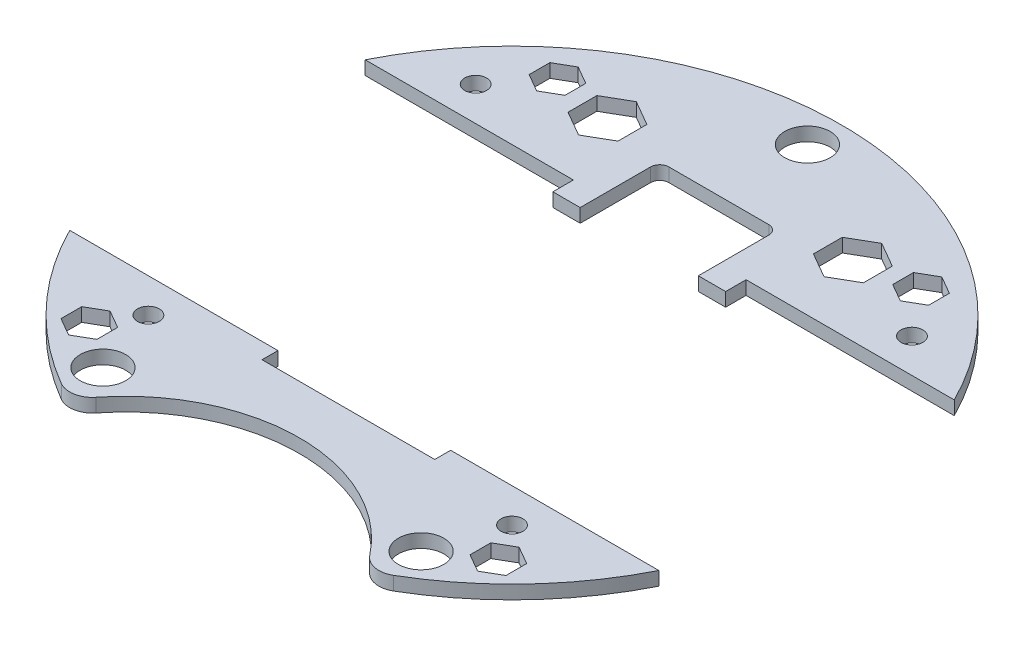
SolidWorks part; units mm, degrees
material "Acrylic (Medium-high impact)"
ref_plane "Front Plane" through (0, 0, 0) normal (0, 0, 1) x (1, 0, 0)
ref_plane "Top Plane" through (0, 0, 0) normal (0, 1, 0) x (1, 0, 0)
ref_plane "Right Plane" through (0, 0, 0) normal (1, 0, 0) x (0, 0, -1)
sketch "Sketch1" plane through (0, 0, 0) normal (0, 1, 0) x (1, 0, 0)
  line L0 (0, -85) -> (-32.4891, -64.8129) construction
  line L1 (0, -85) -> (0, 0) construction
  arc A0 (36.5434, -62.6165) -> (-36.5434, -62.6165) centre (0, 0) ccw
  arc A1 (30.0898, -61.3851) -> (-30.0898, -61.3851) centre (0, -85) ccw
  arc A2 (36.5434, -62.6165) -> (30.0898, -61.3851) centre (34.0231, -58.2982) cw
  arc A3 (-30.0898, -61.3851) -> (-36.5434, -62.6165) centre (-34.0231, -58.2982) cw
  dimension "D1" = 145
  dimension "D2" = 76.5
  dimension "D4" = 5
  dimension "D3" = 85
extrude "Boss-Extrude1" add sketch "Sketch1" along normal blind 3
sketch "solenoid placement" plane through (0, 3, 0) normal (0, 1, 0) x (1, 0, 0)
  line L4 (-19, -36) -> (19, -36)
  line L5 (-19, 28) -> (-19, -36)
  line L6 (19, 28) -> (-19, 28)
  line L7 (19, -36) -> (19, 28)
  line L8 (-19, -36) -> (19, -36)
  line L9 (-19, 28) -> (-19, -36)
  line L10 (19, 28) -> (-19, 28)
  line L11 (19, -36) -> (19, 28)
  dimension "D1" = 0
extrude "Cut-Extrude1" cut sketch "solenoid placement" against normal through all
sketch "Sketch5" plane through (0, 3, 0) normal (0, 1, 0) x (1, 0, 0)
  line L12 (-21.5, 51.1754) -> (-27, 54.3509)
  line L13 (-27, 54.3509) -> (-32.5, 51.1754)
  line L14 (-32.5, 51.1754) -> (-32.5, 44.8246)
  line L15 (-32.5, 44.8246) -> (-27, 41.6491)
  line L16 (-27, 41.6491) -> (-21.5, 44.8246)
  line L17 (-21.5, 44.8246) -> (-21.5, 51.1754)
  line L18 (-21.5, 51.1754) -> (-27, 54.3509)
  line L19 (-27, 54.3509) -> (-32.5, 51.1754)
  line L20 (-32.5, 51.1754) -> (-32.5, 44.8246)
  line L21 (-32.5, 44.8246) -> (-27, 41.6491)
  line L22 (-27, 41.6491) -> (-21.5, 44.8246)
  line L23 (-21.5, 44.8246) -> (-21.5, 51.1754)
  line L24 (21.5, 51.1754) -> (21.5, 44.8246)
  line L25 (21.5, 44.8246) -> (27, 41.6491)
  line L26 (27, 41.6491) -> (32.5, 44.8246)
  line L27 (32.5, 44.8246) -> (32.5, 51.1754)
  line L28 (32.5, 51.1754) -> (27, 54.3509)
  line L29 (27, 54.3509) -> (21.5, 51.1754)
  line L30 (21.5, 51.1754) -> (21.5, 44.8246)
  line L31 (21.5, 44.8246) -> (27, 41.6491)
  line L32 (27, 41.6491) -> (32.5, 44.8246)
  line L33 (32.5, 44.8246) -> (32.5, 51.1754)
  line L34 (32.5, 51.1754) -> (27, 54.3509)
  line L35 (27, 54.3509) -> (21.5, 51.1754)
  dimension "D1" = 0
  dimension "D2" = 0
extrude "Cut-Extrude5" cut sketch "Sketch5" against normal through all
sketch "Sketch6" plane through (0, 3, 0) normal (0, 1, 0) x (1, 0, 0)
  circle A1 centre (40, -40) radius 2.4
  circle A2 centre (40, -40) radius 2.4
  circle A3 centre (-40, -40) radius 2.4
  circle A4 centre (-40, -40) radius 2.4
  circle A5 centre (48, 40) radius 2.4
  circle A6 centre (48, 40) radius 2.4
  circle A7 centre (-48, 40) radius 2.4
  circle A8 centre (-48, 40) radius 2.4
  dimension "D1" = 0
  dimension "D2" = 0
  dimension "D3" = 0
  dimension "D4" = 0
extrude "Cut-Extrude6" cut sketch "Sketch6" against normal through all
sketch "Sketch3" plane through (0, 3, 0) normal (0, 1, 0) x (1, 0, 0)
  line L0 (-19, 28) -> (-19, 32.5)
  line L1 (72.5, -32.5) -> (-72.5, -32.5)
  line L2 (72.5, -32.5) -> (72.5, 32.5)
  line L3 (72.5, 32.5) -> (19, 32.5)
  line L4 (-72.5, -32.5) -> (-72.5, 32.5)
  line L5 (72.5, -32.5) -> (-72.5, 32.5) construction
  line L6 (72.5, 32.5) -> (-72.5, -32.5) construction
  line L7 (-19, 28) -> (19, 28)
  line L8 (19, 28) -> (19, 32.5)
  line L9 (-19, 32.5) -> (-72.5, 32.5)
  arc A0 (36.5434, -62.6165) -> (-36.5434, -62.6165) centre (0, 0) ccw construction
  point P0 (0, 0)
  dimension "D1" = 65
extrude "Cut-Extrude3" cut sketch "Sketch3" against normal through all
sketch "Sketch7" plane through (0, 3, 0) normal (0, 1, 0) x (1, 0, 0)
  line L8 (13, 28) -> (13, 43.5)
  line L9 (-13, 28) -> (13, 28)
  line L10 (-13, 43.5) -> (-13, 28)
  line L11 (11, 45.5) -> (-11, 45.5)
  line L20 (13, 28) -> (13, 43.5)
  line L21 (-13, 28) -> (13, 28)
  line L22 (-13, 43.5) -> (-13, 28)
  line L23 (11, 45.5) -> (-11, 45.5)
  arc A4 (-11, 45.5) -> (-13, 43.5) centre (-11, 43.5) ccw
  arc A5 (13, 43.5) -> (11, 45.5) centre (11, 43.5) ccw
  arc A10 (-11, 45.5) -> (-13, 43.5) centre (-11, 43.5) ccw
  arc A11 (13, 43.5) -> (11, 45.5) centre (11, 43.5) ccw
  dimension "D1" = 0
extrude "Cut-Extrude7" cut sketch "Sketch7" against normal through all
sketch "Sketch8" plane through (0, 3, 0) normal (0, -1, 0) x (1, 0, 0)
  circle A1 centre (35, 55) radius 5
  circle A2 centre (35, 55) radius 5
  circle A3 centre (-35, 55) radius 5
  circle A4 centre (-35, 55) radius 5
  dimension "D1" = 0
  dimension "D2" = 0
extrude "Cut-Extrude9" cut sketch "Sketch8" along normal through all
sketch "Sketch9" plane through (0, 3, 0) normal (0, -1, 0) x (1, 0, 0)
  circle A1 centre (0, -65) radius 5
  circle A2 centre (0, -65) radius 5
  dimension "D1" = 0
extrude "Cut-Extrude11" cut sketch "Sketch9" along normal through all
sketch "Sketch10" plane through (0, 3, 0) normal (0, 1, 0) x (1, 0, 0)
  line L0 (0, 0) -> (0, -22.8708) construction
  line L1 (48.95, -45.7195) -> (45, -43.4389)
  line L2 (45, -43.4389) -> (41.05, -45.7195)
  line L3 (41.05, -45.7195) -> (41.05, -50.2805)
  line L4 (41.05, -50.2805) -> (45, -52.5611)
  line L5 (45, -52.5611) -> (48.95, -50.2805)
  line L6 (48.95, -50.2805) -> (48.95, -45.7195)
  line L7 (-48.95, -50.2805) -> (-48.95, -45.7195)
  line L8 (-45, -52.5611) -> (-48.95, -50.2805)
  line L9 (-41.05, -50.2805) -> (-45, -52.5611)
  line L10 (-41.05, -45.7195) -> (-41.05, -50.2805)
  line L11 (-45, -43.4389) -> (-41.05, -45.7195)
  line L12 (-48.95, -45.7195) -> (-45, -43.4389)
  line L13 (-43.95, 52.2805) -> (-40, 54.5611)
  line L14 (40, 54.5611) -> (36.05, 52.2805)
  line L15 (36.05, 52.2805) -> (36.05, 47.7195)
  line L16 (36.05, 47.7195) -> (40, 45.4389)
  line L17 (40, 45.4389) -> (43.95, 47.7195)
  line L18 (43.95, 47.7195) -> (43.95, 52.2805)
  line L19 (43.95, 52.2805) -> (40, 54.5611)
  line L20 (-43.95, 47.7195) -> (-43.95, 52.2805)
  line L21 (-40, 45.4389) -> (-43.95, 47.7195)
  line L22 (-36.05, 47.7195) -> (-40, 45.4389)
  line L23 (-36.05, 52.2805) -> (-36.05, 47.7195)
  line L24 (-40, 54.5611) -> (-36.05, 52.2805)
  circle A0 centre (45, -48) radius 3.95 construction
  circle A1 centre (-45, -48) radius 3.95 construction
  circle A2 centre (40, 50) radius 3.95 construction
  circle A3 centre (-40, 50) radius 3.95 construction
  dimension "D1" = 7.9
  dimension "D2" = 45
  dimension "D3" = 48
  dimension "D4" = 40
  dimension "D5" = 50
extrude "Cut-Extrude12" cut sketch "Sketch10" against normal through all
equation "\"smallPulleyTeeth\"= 30"
equation "\"largePulleyTeeth\"= 30"
equation "\"eighthThick\"= 3.0mm"
equation "\"sixteenthThick\" = 1.7mm"
equation "\"quarterThick\"=6.0mm"
equation "\"OD\" = 145mm"
equation "\"puckAngle\" = 60.5deg"
equation "\"D1@Sketch1\"=\"OD\""
equation "\"puckDiam\" = 76.5mm"
equation "\"D2@Sketch1\"=\"puckDiam\""
equation "\"D1@Boss-Extrude1\"=\"eighthThick\""
equation "\"axlePress\" = 5.9mm"
equation "\"press\" = 0.2mm"
equation "\"wheelClear\" = 0.3mm"
equation "\"10-32clear\" = 4.8mm"
equation "\"6-32clear\" = 3.3mm"
equation "\"8-32clear\" = 4.0mm"
equation "\"wheelHeight\" = 22mm"
equation "\"wheelWell\" = 65mm"
equation "\"D1@Sketch3\"=\"wheelWell\""
equation "\"puckDist\" = 85mm"
equation "\"scoopFillet\" = 5mm"
equation "\"4-40clear\" = 3.0mm"
equation "\"D3@Sketch1\"=\"puckDist\""
equation "\"D4@Sketch1\"=\"scoopFillet\""
